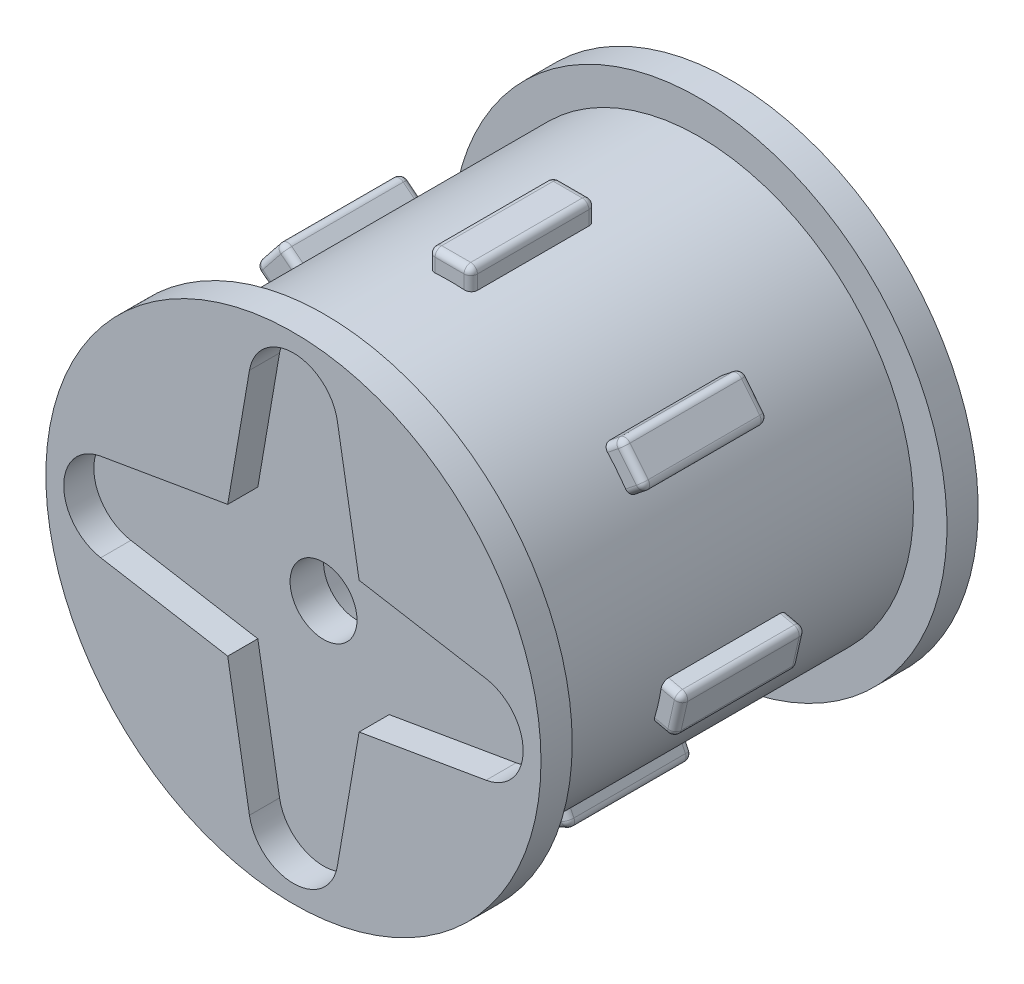
SolidWorks part; units mm, degrees
ref_plane "Ebene vorne" through (0, 0, 0) normal (0, 0, 1) x (1, 0, 0)
ref_plane "Ebene oben" through (0, 0, 0) normal (0, 1, 0) x (1, 0, 0)
ref_plane "Ebene rechts" through (0, 0, 0) normal (1, 0, 0) x (0, 0, -1)
sketch "Skizze1" plane through (0, 0, 0) normal (0, 0, 1) x (1, 0, 0)
  circle A0 centre (0, 0) radius 9.6
  dimension "D1" = 19.2
extrude "Aufsatz-Linear austragen1" add sketch "Skizze1" along normal blind 9.8 and the other way blind 9.8
ref_axis "Rotationsachse" through (0, 0, -9.8) along (0, 0, 1)
sketch "Skizze2" plane through (0, 0, 9.8) normal (0, 0, 1) x (1, 0, 0)
  circle A0 centre (0, 0) radius 11.1
  dimension "D1" = 22.2
extrude "Aufsatz-Linear austragen2" add sketch "Skizze2" against normal blind 1.4
sketch "Skizze3" plane through (0, 0, -9.8) normal (0, 0, -1) x (-1, 0, 0)
  circle A0 centre (0, 0) radius 11.1
  dimension "D1" = 22.2
extrude "Aufsatz-Linear austragen3" add sketch "Skizze3" against normal blind 1.4
sketch "Skizze4" plane through (0, 0, 9.8) normal (0, 0, 1) x (1, 0, 0)
  line L0 (-3.3513, 0.5735) -> (-1.9713, 8.6373)
  line L1 (3.3513, 0.5735) -> (1.9713, 8.6373)
  circle A0 centre (0, 0) radius 3.4
  circle A1 centre (0, 8.3) radius 2
  dimension "D1" = 6.8
  dimension "D3" = 4
  dimension "D2" = 8.3
extrude "Schnitt-Linear austragen1" cut sketch "Skizze4" against normal blind 1.35 contours A1 | A1 L0 A0 L1 | A0 region at (0, 4.7309, 9.8) region at (0, 0, 9.8) region at (0, 8.3, 9.8)
pattern_circular "Kreismuster1" count 4 over 360 about axis through (0, 0, -9.8) along (0, 0, 1) of "Schnitt-Linear austragen1"
sketch "Skizze8" plane through (0, 0, 0) normal (1, 0, 0) x (0, 0, -1)
  line L0 (9.8, 0) -> (9.8, 8)
  line L1 (9.8, -11.1) -> (9.8, 11.1) construction
  line L2 (9.8, 8) -> (8.4, 8)
  line L3 (8.4, 11.1) -> (8.4, -11.1) construction
  line L4 (8.4, 8) -> (-6.95, 3.5)
  line L6 (-6.95, 3.5) -> (-6.95, 0)
  line L7 (-6.95, 0) -> (9.8, 0)
  point P4 (0, 0)
  point P12 (0, 0)
  point P13 (-8.4, 0)
  point P14 (0, 0)
  dimension "D1" = 8
  dimension "D2" = 3.5
  dimension "D3" = 16.75
revolve "Schnitt-Rotation1" cut sketch "Skizze8" angle 360 about axis through (0, 0, -9.8) along (0, 0, 1)
sketch "Skizze9" plane through (0, 0, 8.45) normal (0, 0, 1) x (1, 0, 0)
  circle A0 centre (0, 0) radius 1.5
  dimension "D1" = 3
extrude "Schnitt-Linear austragen2" cut sketch "Skizze9" against normal through all
ref_plane "Schnittebene_Zaehne" through (0, 0, 0) normal (0, 0, -1) x (-1, 0, 0)
sketch "Skizze11" plane through (0, 0, 0) normal (0, 0, -1) x (-1, 0, 0)
  line L0 (0, 0) -> (0, 12.664) construction
  line L6 (-0.95, 8.71) -> (0.95, 8.71)
  line L7 (-0.95, 8.71) -> (-0.95, 10.49)
  line L8 (-0.95, 10.49) -> (0.95, 10.49)
  line L9 (0.95, 8.71) -> (0.95, 10.49)
  line L10 (-0.95, 8.71) -> (0.95, 10.49) construction
  line L11 (-0.95, 10.49) -> (0.95, 8.71) construction
  circle A1 centre (0, 0) radius 9.6 construction
  point P3 (0, 9.6)
  dimension "D1" = 0.89
  dimension "D2" = 1.9
extrude "Aufsatz-Linear austragen4" add sketch "Skizze11" along normal blind 2.8 and the other way blind 2.8
pattern_circular "Kreismuster2" count 7 over 360 about axis through (0, 0, -9.8) along (0, 0, 1) of "Aufsatz-Linear austragen4"
fillet "Verrundung1" radius 0.3 56 edges at (8.2014, 6.5404, 2.8) (7.6091, 7.2831, 0) (8.2014, 6.5404, -2.8) (8.7937, 5.7977, 0) (-8.4274, 5.5055, 2.8) (-7.2428, 6.991, 2.8) (-7.2428, 6.991, -2.8) (-8.4274, 5.5055, -2.8) (-9.5588, -3.1562, -2.8) (-9.9816, -1.3038, -2.8) (-9.5588, -3.1562, 2.8) (-9.9816, -1.3038, 2.8) (-5.2041, -8.6168, -2.8) (-3.4922, -9.4412, -2.8) (-3.4922, -9.4412, 2.8) (-5.2041, -8.6168, 2.8) (5.2041, -8.6168, 2.8) (3.4922, -9.4412, 2.8) (3.4922, -9.4412, -2.8) (5.2041, -8.6168, -2.8) (9.5588, -3.1562, 2.8) (9.5588, -3.1562, -2.8) (9.9816, -1.3038, 2.8) (9.9816, -1.3038, -2.8) (8.4274, 5.5055, 2.8) (8.4274, 5.5055, -2.8) (7.2428, 6.991, -2.8) (7.2428, 6.991, 2.8) (0.95, 10.0214, 2.8) (0.95, 10.0214, -2.8) (-0.95, 10.0214, -2.8) (-0.95, 10.0214, 2.8) (10.4384, -1.4081, 0) (10.227, -2.3342, 2.8) (10.227, -2.3342, -2.8) (10.0156, -3.2604, 0) (4.5514, -9.4512, 2.8) (4.5514, -9.4512, -2.8) (5.4074, -9.039, 0) (3.6955, -9.8634, 0) (-4.5514, -9.4512, 2.8) (-4.5514, -9.4512, -2.8) (-5.4074, -9.039, 0) (-3.6955, -9.8634, 0) (-10.227, -2.3342, 2.8) (-10.227, -2.3342, -2.8) (-10.0156, -3.2604, 0) (-10.4384, -1.4081, 0) (-8.2014, 6.5404, -2.8) (-8.2014, 6.5404, 2.8) (-8.7937, 5.7977, 0) (-7.6091, 7.2831, 0) (0, 10.49, -2.8) (0, 10.49, 2.8) (0.95, 10.49, 0) (-0.95, 10.49, 0)
